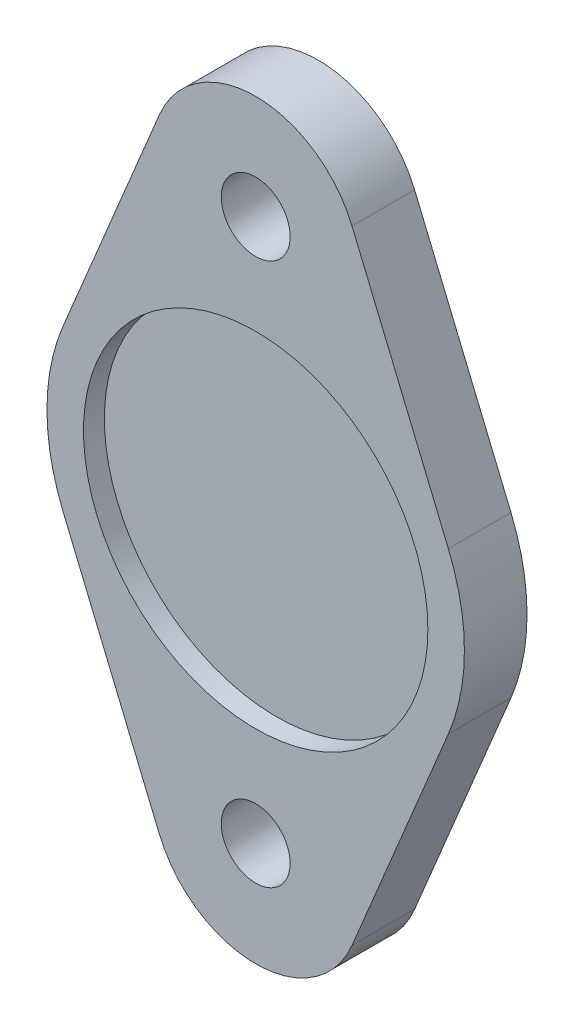
SolidWorks part; units mm, degrees
material "A-玻璃纤维"
ref_plane "前视基准面" through (0, 0, 0) normal (0, 0, 1) x (1, 0, 0)
ref_plane "上视基准面" through (0, 0, 0) normal (0, 1, 0) x (1, 0, 0)
ref_plane "右视基准面" through (0, 0, 0) normal (1, 0, 0) x (0, 0, -1)
sketch "草图1" plane through (0, 0, 0) normal (0, 0, 1) x (1, 0, 0)
  line L0 (-9.2308, 3.8462) -> (-4.6154, 14.9231)
  line L1 (4.6154, 14.9231) -> (9.2308, 3.8462)
  line L2 (0, 0) -> (20.0508, 0) construction
  line L3 (4.6154, -14.9231) -> (9.2308, -3.8462)
  line L4 (-9.2308, -3.8462) -> (-4.6154, -14.9231)
  line L5 (0, -39.2315) -> (0, 33.6284) construction
  circle A0 centre (0, 0) radius 8.25
  circle A1 centre (0, 0) radius 10
  arc A2 (-4.6154, 14.9231) -> (4.6154, 14.9231) centre (0, 13) cw
  arc A3 (-4.6154, -14.9231) -> (4.6154, -14.9231) centre (0, -13) ccw
  circle A4 centre (0, 13) radius 1.65
  circle A5 centre (0, -13) radius 1.65
  dimension "D1" = 16.5
  dimension "D2" = 20
  dimension "D3" = 5
  dimension "D5" = 3.3
  dimension "D4" = 13
extrude "凸台-拉伸1" add sketch "草图1" along normal blind 3 contours A2 L0 A1 L1 A4 | A1 A0 | L4 A3 L3 A1 A5 region at (-6.7083, 9.2951, 0) region at (0, 9.7172, 0) region at (0, -10.2326, 0)
extrude "凸台-拉伸2" add sketch "草图1<3>" along normal blind 2 contours A0 region at (0, 0, 0)
sketch "草图1<3>" plane through (0, 0, 0) normal (0, 0, 1) x (1, 0, 0) same geometry as "草图1"
